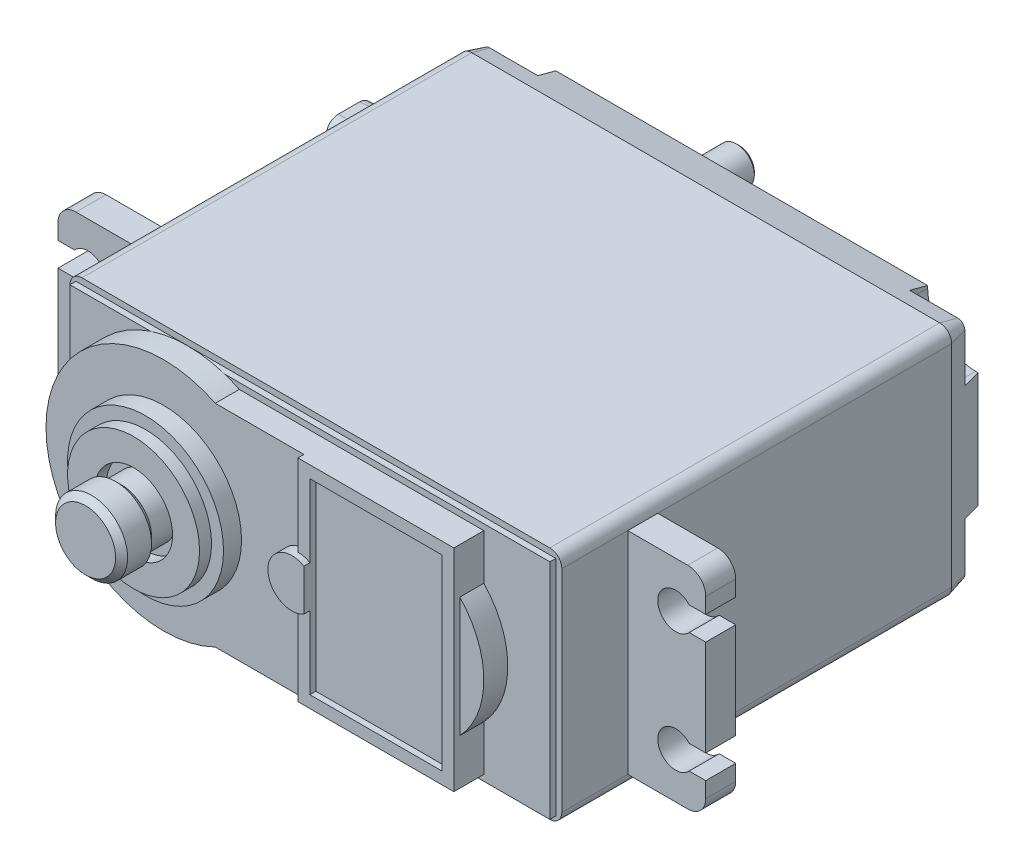
SolidWorks part; units mm, degrees
ref_plane "Front Plane" through (0, 0, 0) normal (0, 0, 1) x (1, 0, 0)
ref_plane "Top Plane" through (0, 0, 0) normal (0, 1, 0) x (1, 0, 0)
ref_plane "Right Plane" through (0, 0, 0) normal (1, 0, 0) x (0, 0, -1)
sketch "Sketch1" plane through (0, 0, 0) normal (0, 1, 0) x (1, 0, 0)
  line L1 (0, 0) -> (41, 0)
  line L2 (0, 0) -> (0, -35.5)
  line L3 (0, -35.5) -> (41, -35.5)
  line L4 (41, 0) -> (41, -35.5)
  dimension "D1" = 41
  dimension "D2" = 35.5
extrude "Boss-Extrude1" add sketch "Sketch1" along normal blind 19.6
sketch "Sketch5" plane through (41, 0, 0) normal (1, 0, 0) x (0, 0, -1)
  line L0 (-35.5, 19.6) -> (-35.5, 0) construction
  line L1 (-30, 18.6) -> (-27.5, 18.6)
  line L2 (-30, 18.6) -> (-30, 1)
  line L3 (-30, 1) -> (-27.5, 1)
  line L4 (-27.5, 18.6) -> (-27.5, 1)
  line L5 (-35.5, 0) -> (0, 0) construction
  line L6 (-35.5, 19.6) -> (0, 19.6) construction
  dimension "D1" = 5.5
  dimension "D2" = 2.5
  dimension "D3" = 1
  dimension "D4" = 1
extrude "Boss-Extrude3" add sketch "Sketch5" along normal blind 6.5
sketch "Sketch6" plane through (0, 0, 30) normal (0, 0, 1) x (1, 0, 0)
  line L2 (47.5, 18.6) -> (47.5, 1) construction
  line L3 (47.5, 15.8) -> (46.118, 15.8)
  line L4 (41, 14.8) -> (47.5, 14.8) construction
  line L5 (47.5, 13.8) -> (46.118, 13.8)
  line L6 (47.5, 15.8) -> (47.5, 13.8)
  line L7 (47.5, 9.8) -> (41, 9.8) construction
  line L8 (47.5, 3.8) -> (47.5, 5.8)
  line L9 (47.5, 5.8) -> (46.118, 5.8)
  line L10 (47.5, 3.8) -> (46.118, 3.8)
  line L11 (41, 18.6) -> (41, 1) construction
  line L12 (41, 19.6) -> (41, 0) construction
  arc A0 (46.118, 15.8) -> (46.118, 13.8) centre (45, 14.8) ccw
  arc A1 (46.118, 5.8) -> (46.118, 3.8) centre (45, 4.8) ccw
  dimension "D1" = 10
  dimension "D3" = 3
  dimension "D4" = 2.5
  dimension "D5" = 1
extrude "Cut-Extrude3" cut sketch "Sketch6" against normal up to next
sketch "Sketch8" plane through (0, 0, 35.5) normal (0, 0, 1) x (1, 0, 0)
  line L0 (0.5, 19.1) -> (0.5, 0.5)
  line L1 (0.5, 0.5) -> (40.5, 0.5)
  line L2 (40.5, 0.5) -> (40.5, 19.1)
  line L3 (40.5, 19.1) -> (0.5, 19.1)
  line L4 (0, 0) -> (41, 0)
  line L5 (41, 0) -> (41, 19.6)
  line L6 (41, 19.6) -> (0, 19.6)
  line L7 (0, 19.6) -> (0, 0)
  line L8 (0, 0) -> (41, 0) construction
  line L9 (41, 0) -> (41, 19.6) construction
  line L10 (41, 19.6) -> (0, 19.6) construction
  line L11 (0, 19.6) -> (0, 0) construction
  dimension "D1" = 0
  dimension "D2" = 0.5
extrude "Boss-Extrude4" add sketch "Sketch8" along normal blind 0.5
sketch "Sketch10" plane through (0, 0, 36) normal (0, 0, 1) x (1, 0, 0)
  line L1 (35, 18.6) -> (14.6128, 18.6)
  line L2 (35, 4.8) -> (35, 1)
  line L3 (35, 1) -> (14.6128, 1)
  line L4 (35, 18.6) -> (35, 14.8)
  line L6 (41, 19.6) -> (41, 0) construction
  line L7 (0.5, 0.5) -> (40.5, 0.5) construction
  line L8 (0, 19.6) -> (41, 19.6) construction
  line L9 (0, 0) -> (41, 0) construction
  line L10 (0.5, 19.1) -> (0.5, 0.5) construction
  line L11 (40.5, 19.1) -> (0.5, 19.1) construction
  arc A0 (14.6128, 18.6) -> (14.6128, 1) centre (10.3, 9.8) ccw
  arc A1 (35, 4.8) -> (35, 14.8) centre (29.75, 9.8) ccw
  dimension "D3" = 10
  dimension "D2" = 2
  dimension "D1" = 6
  dimension "D4" = 0.5
  dimension "D5" = 0.5
extrude "Boss-Extrude6" add sketch "Sketch10" along normal blind 2
sketch "Sketch11" plane through (0, 0, 38) normal (0, 0, 1) x (1, 0, 0)
  line L0 (35, 18.6) -> (14.6128, 18.6) construction
  line L1 (22, 18.6) -> (35, 18.6)
  line L2 (22, 18.6) -> (22, 11.8)
  line L3 (22, 1) -> (35, 1)
  line L4 (35, 18.6) -> (35, 1)
  line L5 (23, 17.6) -> (23, 2)
  line L6 (23, 2) -> (34, 2)
  line L7 (34, 17.6) -> (34, 2)
  line L8 (23, 17.6) -> (34, 17.6)
  line L9 (22, 18.6) -> (22, 1) construction
  line L10 (22, 7.8) -> (22, 1)
  arc A0 (22, 11.8) -> (22, 7.8) centre (22, 9.8) ccw
  dimension "D3" = 4
  dimension "D4" = 8.8
  dimension "D1" = 13
  dimension "D2" = 1
  dimension "D5" = 2
extrude "Boss-Extrude7" add sketch "Sketch11" along normal blind 0.5
sketch "Sketch12" plane through (0, 0, 38.5) normal (0, 0, 1) x (1, 0, 0)
  line L0 (23, 11.5321) -> (23, 8.0679)
  line L1 (34, 17.6) -> (23, 17.6) construction
  arc A0 (23, 11.5321) -> (23, 8.0679) centre (22, 9.8) ccw
  dimension "D1" = 6.0679
extrude "Boss-Extrude8" add sketch "Sketch12" along normal blind 0.5
sketch "Sketch13" plane through (0, 0, 38) normal (0, 0, 1) x (1, 0, 0)
  circle A0 centre (10.3, 9.8) radius 6.5
  arc A1 (14.6128, 18.6) -> (14.6128, 1) centre (10.3, 9.8) ccw construction
  dimension "D1" = 13
extrude "Boss-Extrude9" add sketch "Sketch13" along normal blind 1.5
sketch "Sketch14" plane through (0, 0, 39.5) normal (0, 0, 1) x (1, 0, 0)
  circle A0 centre (10.3, 9.8) radius 5.5
  circle A1 centre (10.3, 9.8) radius 6.5 construction
  dimension "D1" = 11
extrude "Boss-Extrude10" add sketch "Sketch14" along normal blind 1
sketch "Sketch15" plane through (0, 0, 40.5) normal (0, 0, 1) x (1, 0, 0)
  circle A0 centre (10.3, 9.8) radius 3.25
  circle A1 centre (10.3, 9.8) radius 5.5 construction
  dimension "D1" = 6.5
extrude "Cut-Extrude4" cut sketch "Sketch15" against normal blind 1
sketch "Sketch16" plane through (0, 0, 39.5) normal (0, 0, 1) x (1, 0, 0)
  circle A0 centre (10.3, 9.8) radius 2.5
  circle A1 centre (10.3, 9.8) radius 3.25 construction
  dimension "D1" = 5
extrude "Boss-Extrude11" add sketch "Sketch16" along normal blind 2 separate body
sketch "Sketch18" plane through (0, 0, 41.5) normal (0, 0, 1) x (1, 0, 0)
  circle A1 centre (10.3, 9.8) radius 3
  circle A2 centre (10.3, 9.8) radius 2.5 construction
  dimension "D1" = 6
extrude "Boss-Extrude12" add sketch "Sketch18" along normal blind 3
sketch "Sketch19" plane through (0, 19.6, 0) normal (0, 1, 0) x (1, 0, 0)
  line L0 (41, 0) -> (0, 0) construction
  line L1 (0, -35.5) -> (41, -35.5) construction
  point P2 (20.5, 0)
  point P3 (20.5, -35.5)
  point P4 (20.5, 0)
sketch "Sketch20" plane through (0, 0, 0) normal (0, -1, 0) x (1, 0, 0)
  line L0 (0, 35.5) -> (41, 35.5) construction
  point P0 (20.5, 35.5)
ref_plane "Plane1" through (20.5, 0, 0) normal (1, 0, 0) x (0, 0, -1)
mirror "Mirror1" about plane through (20.5, 0, 0) normal (1, 0, 0) of "Boss-Extrude3"
mirror "Mirror2" about plane through (20.5, 0, 0) normal (1, 0, 0) of "Cut-Extrude3"
sketch "Sketch21" plane through (0, 0, 0) normal (-1, 0, 0) x (0, 0, 1)
  line L0 (0, 19.6) -> (35.5, 19.6) construction
  line L1 (3, 13.1) -> (7.5, 13.1)
  line L2 (3, 13.1) -> (3, 6.5)
  line L3 (3, 6.5) -> (7.5, 6.5)
  line L4 (7.5, 13.1) -> (7.5, 6.5)
  line L5 (0, 0) -> (35.5, 0) construction
  line L6 (0, 19.6) -> (0, 0) construction
  dimension "D1" = 6.5
  dimension "D2" = 6.5
  dimension "D3" = 3
  dimension "D4" = 4.5
extrude "Boss-Extrude13" add sketch "Sketch21" along normal blind 7 draft 3 separate body
sketch "Sketch22" plane through (0, 0, 0) normal (0, 0, -1) x (-1, 0, 0)
  line L0 (0, 19.6) -> (-5, 19.6)
  line L1 (-41, 19.6) -> (0, 19.6) construction
  line L2 (-5, 19.6) -> (-5, 18.6)
  line L3 (-1, 14.6) -> (0, 14.6)
  line L4 (0, 19.6) -> (0, 0) construction
  line L5 (0, 14.6) -> (0, 19.6)
  line L6 (-41, 9.8) -> (0, 9.8) construction
  line L7 (-41, 1) -> (-41, 18.6) construction
  line L8 (-20.5, 19.6) -> (-20.5, 0) construction
  line L9 (-41, 0) -> (0, 0) construction
  line L10 (0, 5) -> (0, 0)
  line L11 (-1, 5) -> (0, 5)
  line L12 (-5, 0) -> (-5, 1)
  line L13 (0, 0) -> (-5, 0)
  line L14 (-41, 0) -> (-36, 0)
  line L15 (-36, 0) -> (-36, 1)
  line L16 (-40, 5) -> (-41, 5)
  line L17 (-41, 5) -> (-41, 0)
  line L18 (-41, 14.6) -> (-41, 19.6)
  line L19 (-40, 14.6) -> (-41, 14.6)
  line L20 (-36, 19.6) -> (-36, 18.6)
  line L21 (-41, 19.6) -> (-36, 19.6)
  arc A0 (-5, 18.6) -> (-1, 14.6) centre (-1, 18.6) ccw
  arc A1 (-5, 1) -> (-1, 5) centre (-1, 1) cw
  arc A2 (-36, 1) -> (-40, 5) centre (-40, 1) ccw
  arc A3 (-36, 18.6) -> (-40, 14.6) centre (-40, 18.6) cw
  dimension "D1" = 5
  dimension "D2" = 5
  dimension "D3" = 1
fillet "Fillet1" radius 1 4 edges at (0, 0, 17.75) (0, 19.6, 17.75) (41, 19.6, 17.75) (41, 0, 17.75)
fillet "Fillet2" radius 1.5 4 edges at (-6.5, 18.6, 28.75) (-6.5, 1, 28.75) (47.5, 1, 28.75) (47.5, 18.6, 28.75)
chamfer "Chamfer1" distance 0.5 angle 45 1 edges at (13.3, 9.8, 44.5)
chamfer "Chamfer2" distance 0.5 angle 45 1 edges at (13.3, 9.8, 41.5)
fillet "Fillet5" radius 1 4 edges at (-3.5, 6.6834, 3.1834) (-3.5, 6.6834, 7.3166) (-3.5, 12.9166, 7.3166) (-3.5, 12.9166, 3.1834)
chamfer "Chamfer3" distance 3 angle 15 8 edges at (40.7071, 0.2929, 0) (41, 9.8, 0) (40.7071, 19.3071, 0) (20.5, 19.6, 0) (0.2929, 19.3071, 0) (0, 9.8, 0) (0.2929, 0.2929, 0) (20.5, 0, 0) first distance on face at (40.7357, 0.5976, 21.4167) first distance on face at (41, 9.8, 13.75) first distance on face at (40.7357, 19.0024, 21.4167) first distance on face at (20.5, 19.6, 17.75) first distance on face at (0.2643, 19.0024, 21.4167) first distance on face at (0, 9.8, 13.75) first distance on face at (0.2643, 0.5976, 21.4167) first distance on face at (20.5, 0, 17.75)
extrude "Cut-Extrude5" cut sketch "Sketch22" against normal blind 1.5
sketch "Sketch30" plane through (0, 0, 1.5) normal (0, 0, -1) x (-1, 0, 0)
  line L2 (-20.5, 18.7962) -> (-20.5, 0.8038) construction
  line L3 (-5, 18.7962) -> (-36, 18.7962) construction
  line L4 (-36, 0.8038) -> (-5, 0.8038) construction
  line L5 (-0.8038, 9.8) -> (-40.1962, 9.8) construction
  line L6 (-0.8038, 5) -> (-0.8038, 14.6) construction
  line L7 (-40.1962, 14.6) -> (-40.1962, 5) construction
sketch "Sketch34" plane through (0, 0, 0) normal (0, 0, -1) x (-1, 0, 0)
  circle A0 centre (-10.3, 9.8) radius 1.5
  dimension "D1" = 3
extrude "Boss-Extrude15" add sketch "Sketch34" along normal blind 10 separate body
sketch "Sketch35" plane through (0, 0, 0) normal (0, 0, -1) x (-1, 0, 0)
  line L0 (-0.8038, 5) -> (-0.8038, 14.6) construction
  line L1 (-7.55, 11.3877) -> (-10.3, 12.9754)
  line L2 (-10.3, 12.9754) -> (-13.05, 11.3877)
  line L3 (-13.05, 11.3877) -> (-13.05, 8.2123)
  line L4 (-13.05, 8.2123) -> (-10.3, 6.6246)
  line L5 (-10.3, 6.6246) -> (-7.55, 8.2123)
  line L6 (-7.55, 8.2123) -> (-7.55, 11.3877)
  circle A0 centre (-10.3, 9.8) radius 2.75 construction
  circle A1 centre (-10.3, 9.8) radius 1.5
  dimension "D1" = 5.5
extrude "Boss-Extrude16" add sketch "Sketch35" along normal blind 2.5 separate body
chamfer "Chamfer4" distance 0.25 angle 45 1 edges at (8.8, 9.8, -10)
chamfer "Chamfer5" distance 0.25 angle 45 12 edges at (8.925, 7.4184, -2.5) (11.675, 7.4184, -2.5) (13.05, 9.8, -2.5) (11.675, 12.1816, -2.5) (8.925, 12.1816, -2.5) (7.55, 9.8, -2.5) (8.925, 7.4184, 0) (11.675, 7.4184, 0) (13.05, 9.8, 0) (7.55, 9.8, 0) (8.925, 12.1816, 0) (11.675, 12.1816, 0)
ref_plane "Plane2" through (0, 0, 42) normal (0, 0, 1) x (1, 0, 0)
